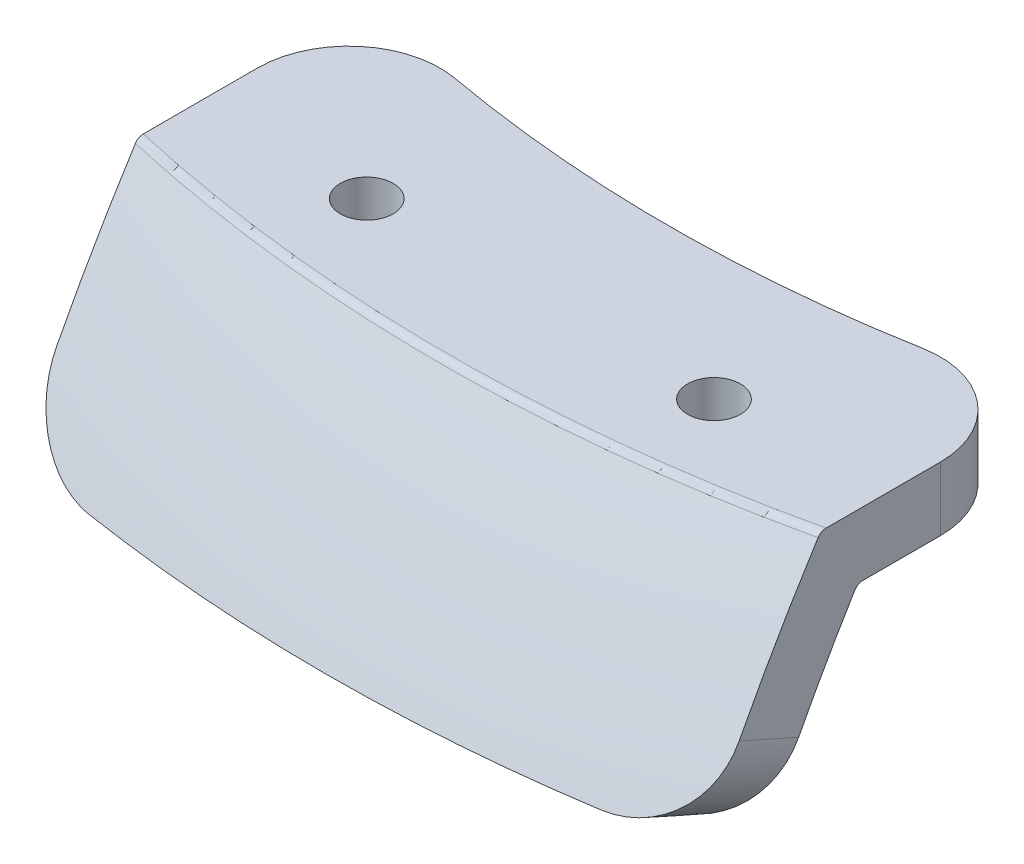
SolidWorks part; units mm, degrees
material "Polyether Polyol"
ref_plane "Front Plane" through (0, 0, 0) normal (0, 0, 1) x (1, 0, 0)
ref_plane "Top Plane" through (0, 0, 0) normal (0, 1, 0) x (1, 0, 0)
ref_plane "Right Plane" through (0, 0, 0) normal (1, 0, 0) x (0, 0, -1)
sketch "Sketch1" plane through (0, 0, 0) normal (1, 0, 0) x (0, 0, -1)
  line L0 (-182.289, 174.265) -> (-175.9097, 171.3832) construction
  line L1 (-169.539, 198.0637) -> (-144.6985, 198.0637) construction
  line L9 (-144.6985, 198.0637) -> (-144.6985, 191.0637) construction
  line L10 (-144.6985, 191.0637) -> (-165.6174, 191.0637) construction
  line L11 (-182.289, 174.265) -> (-175.9097, 171.3832)
  line L12 (-169.539, 198.0637) -> (-144.6985, 198.0637)
  line L13 (-144.6985, 198.0637) -> (-144.6985, 191.0637)
  line L14 (-144.6985, 191.0637) -> (-165.6174, 191.0637)
  line L15 (0, 0) -> (0, 91.9198) construction
  arc A5 (-165.6174, 191.0637) -> (-175.9097, 171.3832) centre (0, 91.9198) ccw construction
  arc A6 (-169.539, 198.0637) -> (-182.289, 174.265) centre (0, 91.9198) ccw construction
  arc A7 (-165.6174, 191.0637) -> (-175.9097, 171.3832) centre (0, 91.9198) ccw
  arc A8 (-169.539, 198.0637) -> (-182.289, 174.265) centre (0, 91.9198) ccw
revolve "Revolve1" add sketch "Sketch1" angle 30 mid plane about L15
sketch "Sketch2" plane through (0, 0, 0) normal (-1, 0, 0) x (0, 0, 1)
  line L0 (0, 91.9198) -> (171.9865, 179.5513) construction
  line L3 (0, -200000) -> (0, 218797.9879) construction
  arc A0 (175.9097, 171.3832) -> (165.6174, 191.0637) centre (0, 91.9198) ccw construction
  dimension "D1" = 63
ref_plane "Plane1" through (0, 72.9744, -37.1823) normal (0, -0.891, 0.454) x (0, 0.454, 0.891)
sketch "Sketch4" plane through (0, 72.9744, -37.1823) normal (0, -0.891, 0.454) x (0, 0.454, 0.891)
  line L0 (219.8801, 19.237) -> (239.1484, 20.9228) construction
  line L1 (219.7494, 20.7313) -> (239.0177, 22.4171)
  line L2 (219.7494, 20.7313) -> (219.8801, 19.237)
  line L3 (41.7307, 0) -> (234.7557, 0) construction
  line L4 (219.8801, 19.237) -> (239.1484, 20.9228)
  line L5 (239.0177, 22.4171) -> (239.1484, 20.9228)
  dimension "D1" = 3
  dimension "D2" = 5
revolve "Cut-Revolve1" cut sketch "Sketch4" angle 360 about L0
mirror "Mirror1" about plane through (0, 0, 0) normal (1, 0, 0) of "Cut-Revolve1"
sketch "Sketch5" plane through (0, 0, 0) normal (0, 1, 0) x (1, 0, 0)
  line L1 (37.4507, -139.768) -> (-37.4507, -139.768)
  line L2 (37.4507, -139.768) -> (37.4507, -182.289)
  line L3 (37.4507, -182.289) -> (-37.4507, -182.289)
  line L4 (-37.4507, -139.768) -> (-37.4507, -182.289)
  arc A0 (-47.1799, -176.0776) -> (47.1799, -176.0776) centre (0, 0) ccw construction
extrude "Cut-Extrude2" cut sketch "Sketch5" along normal through all flip side to cut
fillet "Fillet1" radius 10 4 edges at (-37.4507, 194.5637, 139.768) (37.4507, 194.5637, 139.768)
fillet "Fillet2" radius 1 2 edges at (0, 198.0637, 169.539) (0, 191.0637, 165.6174)
sketch "Sketch6" plane through (0, 198.0637, 0) normal (0, 1, 0) x (1, 0, 0)
  circle A0 centre (19.05, -158.6742) radius 2.9 construction
  circle A1 centre (-19.05, -158.6742) radius 2.9 construction
  circle A2 centre (19.05, -158.6742) radius 2.9
  circle A3 centre (-19.05, -158.6742) radius 2.9
extrude "Cut-Extrude3" cut sketch "Sketch6" against normal through all
